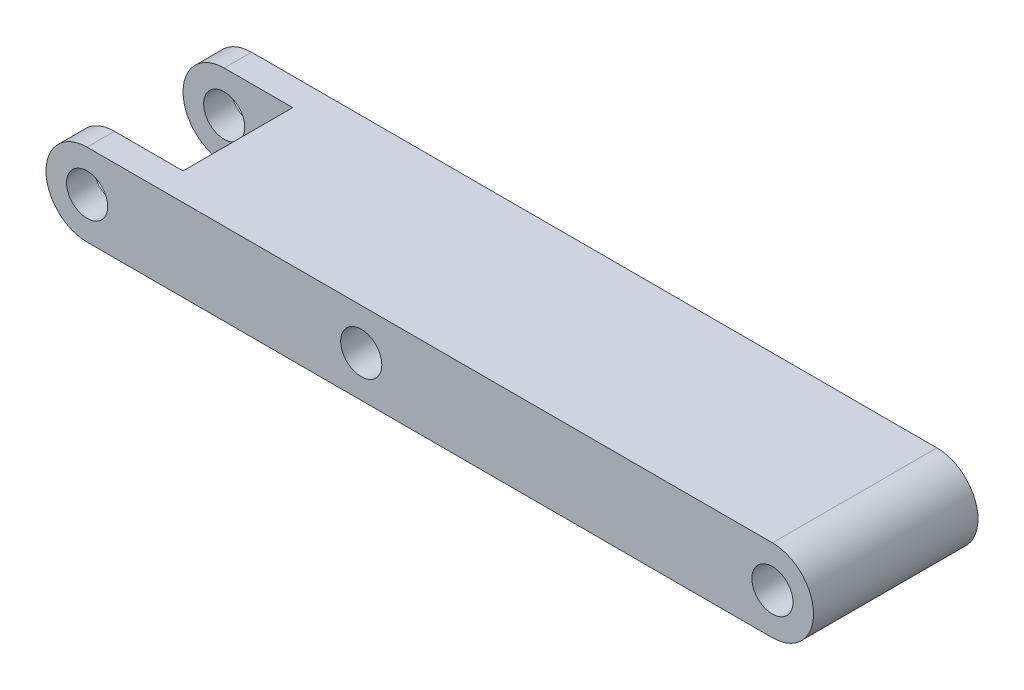
SolidWorks part; units mm, degrees
ref_plane "Front Plane" through (0, 0, 0) normal (0, 0, 1) x (1, 0, 0)
ref_plane "Top Plane" through (0, 0, 0) normal (0, 1, 0) x (1, 0, 0)
ref_plane "Right Plane" through (0, 0, 0) normal (1, 0, 0) x (0, 0, -1)
sketch "Sketch1" plane through (0, 0, 0) normal (0, 0, 1) x (1, 0, 0)
  line L0 (-25, 0) -> (25, 0) construction
  line L1 (-25, 3) -> (25, 3)
  line L2 (-25, -3) -> (25, -3)
  arc A0 (-25, 3) -> (-25, -3) centre (-25, 0) ccw
  arc A1 (25, -3) -> (25, 3) centre (25, 0) ccw
  circle A2 centre (-25, 0) radius 1.5
  circle A3 centre (25, 0) radius 1.5
  circle A4 centre (-5, 0) radius 1.5
  point P2 (0, 0)
  point P14 (-9, 0)
  dimension "D1" = 3
  dimension "D2" = 20
  dimension "D4" = 3
  dimension "D3" = 50
extrude "Boss-Extrude1" add sketch "Sketch1" along normal blind 12
sketch "Sketch3" plane through (0, 3, 0) normal (0, 1, 0) x (1, 0, 0)
  line L1 (25, 0) -> (-25, 0) construction
  line L2 (-35.2635, -2) -> (-20, -2)
  line L3 (-35.2635, -2) -> (-35.2635, -10)
  line L4 (-35.2635, -10) -> (-20, -10)
  line L5 (-20, -2) -> (-20, -10)
  line L8 (-25, -12) -> (-25, 0) construction
  point P0 (-31.9259, -6.0219)
  dimension "D1" = 8
  dimension "D2" = 2
  dimension "D3" = 5
extrude "Cut-Extrude1" cut sketch "Sketch3" against normal blind 10 contours L4 L5 L2 L3
